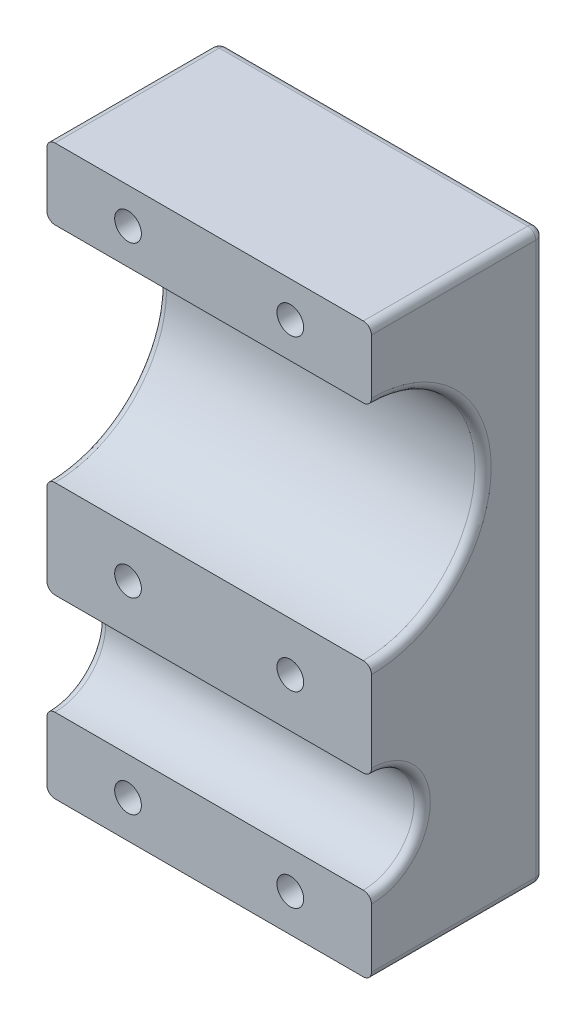
SolidWorks part; units mm, degrees
note: The reader was unsure of these and kept them because the rebuilt part matched: shared geometry of "Sketch5<3>".
ref_plane "Front Plane" through (0, 0, 0) normal (0, 0, 1) x (1, 0, 0)
ref_plane "Top Plane" through (0, 0, 0) normal (0, 1, 0) x (1, 0, 0)
ref_plane "Right Plane" through (0, 0, 0) normal (1, 0, 0) x (0, 0, -1)
sketch "Sketch1" plane through (0, 0, 0) normal (1, 0, 0) x (0, 0, -1)
  line L1 (0, 0) -> (53.975, 0)
  line L2 (0, 0) -> (0, 88.9)
  line L3 (0, 88.9) -> (53.975, 88.9)
  line L4 (53.975, 0) -> (53.975, 88.9)
  circle A0 centre (26.9875, 19.685) radius 7.9375
  circle A1 centre (26.9875, 60.325) radius 17.4625
  point P11 (26.9875, 88.9)
  dimension "D1" = 15.875
  dimension "D2" = 34.925
  dimension "D5" = 40.64
  dimension "D3" = 53.975
  dimension "D4" = 88.9
  dimension "D6" = 28.575
extrude "Boss-Extrude1" add sketch "Sketch1" along normal blind 50.8 contours A1 | A0 | L4 L3 L2 L1
sketch "Sketch5" plane through (0, 0, 0) normal (0, 0, 1) x (1, 0, 0)
  circle A0 centre (38.1, 35.2425) radius 2.09
  circle A1 centre (38.1, 35.2425) radius 3.6
  circle A2 centre (12.7, 83.3438) radius 2.09
  circle A3 centre (12.7, 83.3438) radius 3.6
  circle A4 centre (38.1, 83.3438) radius 2.09
  circle A5 centre (38.1, 83.3438) radius 3.6
  circle A6 centre (12.7, 35.2425) radius 2.09
  circle A7 centre (12.7, 35.2425) radius 3.6
  circle A8 centre (38.1, 5.8737) radius 2.09
  circle A9 centre (38.1, 5.8737) radius 3.6
  circle A10 centre (12.7, 5.8737) radius 2.09
  circle A11 centre (12.7, 5.8737) radius 3.6
  dimension "D3" = 4.18
  dimension "D4" = 4.18
  dimension "D5" = 4.18
  dimension "D6" = 4.18
  dimension "D7" = 4.18
  dimension "D8" = 4.18
  dimension "D9" = 7.2
  dimension "D10" = 7.2
  dimension "D11" = 7.2
  dimension "D12" = 7.2
  dimension "D13" = 7.2
  dimension "D14" = 7.2
  dimension "D1" = 25.4
  dimension "D2" = 12.7
extrude "Cut-Extrude1" cut sketch "Sketch5" against normal through all contours A2 | A6 | A4 | A0 | A10 | A8
extrude "Cut-Extrude2" cut sketch "Sketch5<3>" against normal blind 4.064 contours A3 | A5 | A1 | A7 | A11 | A9
sketch "Sketch5<3>" plane through (0, 0, 0) normal (0, 0, 1) x (1, 0, 0) same geometry as "Sketch5"
sketch "Sketch6" plane through (0, 0, -53.975) normal (0, 0, -1) x (-1, 0, 0)
  line L109 (-34.0286, 83.3438) -> (-36.0643, 86.8697)
  line L110 (-36.0643, 86.8697) -> (-40.1357, 86.8697)
  line L111 (-40.1357, 86.8697) -> (-42.1715, 83.3438)
  line L112 (-42.1715, 83.3438) -> (-40.1357, 79.8178)
  line L113 (-40.1357, 79.8178) -> (-36.0643, 79.8178)
  line L114 (-36.0643, 79.8178) -> (-34.0286, 83.3438)
  line L115 (-8.6286, 83.3438) -> (-10.6643, 86.8697)
  line L116 (-10.6643, 86.8697) -> (-14.7357, 86.8697)
  line L117 (-14.7357, 86.8697) -> (-16.7714, 83.3438)
  line L118 (-16.7714, 83.3438) -> (-14.7357, 79.8178)
  line L119 (-14.7357, 79.8178) -> (-10.6643, 79.8178)
  line L120 (-10.6643, 79.8178) -> (-8.6286, 83.3438)
  line L121 (-8.6286, 35.2425) -> (-10.6643, 38.7685)
  line L122 (-10.6643, 38.7685) -> (-14.7357, 38.7685)
  line L123 (-14.7357, 38.7685) -> (-16.7714, 35.2425)
  line L124 (-16.7714, 35.2425) -> (-14.7357, 31.7165)
  line L125 (-14.7357, 31.7165) -> (-10.6643, 31.7165)
  line L126 (-10.6643, 31.7165) -> (-8.6286, 35.2425)
  line L127 (-34.0286, 35.2425) -> (-36.0643, 38.7685)
  line L128 (-36.0643, 38.7685) -> (-40.1357, 38.7685)
  line L129 (-40.1357, 38.7685) -> (-42.1714, 35.2425)
  line L130 (-42.1714, 35.2425) -> (-40.1357, 31.7165)
  line L131 (-40.1357, 31.7165) -> (-36.0643, 31.7165)
  line L132 (-36.0643, 31.7165) -> (-34.0286, 35.2425)
  line L133 (-34.0286, 5.8737) -> (-36.0643, 9.3997)
  line L134 (-36.0643, 9.3997) -> (-40.1357, 9.3997)
  line L135 (-40.1357, 9.3997) -> (-42.1715, 5.8737)
  line L136 (-42.1715, 5.8737) -> (-40.1357, 2.3478)
  line L137 (-40.1357, 2.3478) -> (-36.0643, 2.3478)
  line L138 (-36.0643, 2.3478) -> (-34.0286, 5.8737)
  line L139 (-8.6286, 5.8737) -> (-10.6643, 9.3997)
  line L140 (-10.6643, 9.3997) -> (-14.7357, 9.3997)
  line L141 (-14.7357, 9.3997) -> (-16.7715, 5.8737)
  line L142 (-16.7715, 5.8737) -> (-14.7357, 2.3478)
  line L143 (-14.7357, 2.3478) -> (-10.6643, 2.3478)
  line L144 (-10.6643, 2.3478) -> (-8.6286, 5.8737)
  circle A0 centre (-38.1, 83.3438) radius 4.0714 construction
  circle A1 centre (-12.7, 83.3438) radius 4.0714 construction
  circle A2 centre (-12.7, 35.2425) radius 4.0714 construction
  circle A3 centre (-38.1, 35.2425) radius 4.0714 construction
  circle A4 centre (-38.1, 5.8737) radius 4.0714 construction
  circle A5 centre (-12.7, 5.8737) radius 4.0714 construction
  circle M1 centre (-12.7, 5.8737) radius 2.09
  circle M2 centre (-38.1, 35.2425) radius 2.09
  circle M3 centre (-38.1, 83.3438) radius 2.09
  circle M4 centre (-12.7, 35.2425) radius 2.09
  circle M5 centre (-38.1, 5.8737) radius 2.09
  dimension "D1" = 8.1429
  dimension "D2" = 8.1429
  dimension "D3" = 8.1429
  dimension "D4" = 8.1429
  dimension "D5" = 8.1429
  dimension "D6" = 8.1429
extrude "Cut-Extrude3" cut sketch "Sketch6" against normal blind 2.54 contours L119 L120 L115 L116 L117 L118 M3 | L125 L126 L121 L122 L123 L124 M2 | L131 L132 L127 L128 L129 L130 M4 | L143 L144 L139 L140 L141 L142 M5 | L137 L138 L133 L134 L135 L136 M1
fillet "Fillet1" radius 1.27 16 edges at (25.4, 0, 0) (25.4, 0, -53.975) (50.8, 19.685, -34.925) (0, 19.685, -34.925) (0, 0, -26.9875) (50.8, 0, -26.9875) (50.8, 60.325, -44.45) (0, 60.325, -44.45) (0, 44.45, 0) (50.8, 44.45, 0) (0, 44.45, -53.975) (50.8, 44.45, -53.975) (25.4, 88.9, 0) (0, 88.9, -26.9875) (50.8, 88.9, -26.9875) (25.4, 88.9, -53.975)
ref_plane "Plane1" through (0, 0, -26.9875) normal (0, 0, 1) x (1, 0, 0)
other "SurfaceCut1" flip cut yes
